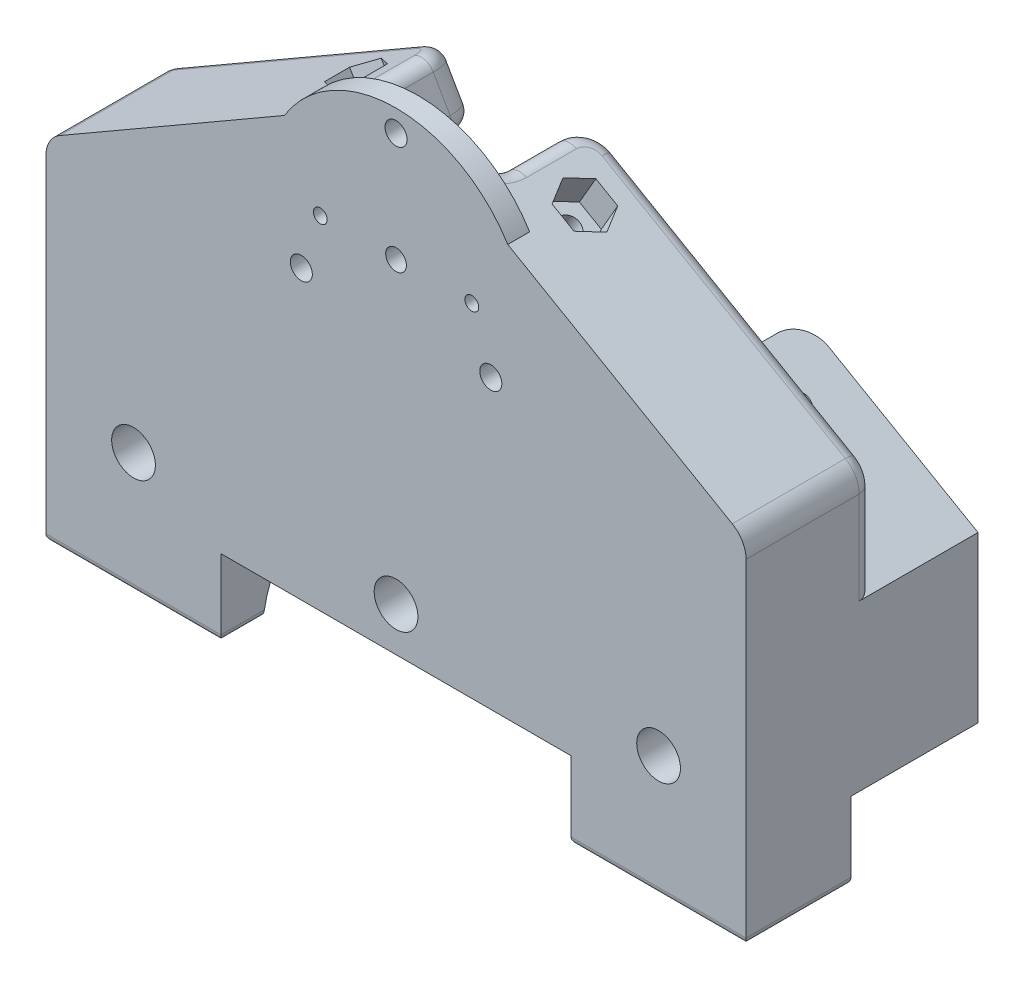
SolidWorks part; units mm, degrees
ref_plane "Front Plane" through (0, 0, 0) normal (0, 0, 1) x (1, 0, 0)
ref_plane "Top Plane" through (0, 0, 0) normal (0, 1, 0) x (1, 0, 0)
ref_plane "Right Plane" through (0, 0, 0) normal (1, 0, 0) x (0, 0, -1)
sketch "Sketch1" plane through (0, 0, 0) normal (0, 0, 1) x (1, 0, 0)
  line L0 (0, 0) -> (101.6, 0)
  line L2 (17.3289, 36.6882) -> (44.45, 52.3466) construction
  line L3 (0, 23.9337) -> (0, 0)
  line L5 (101.6, 23.9337) -> (101.6, 0)
  line L6 (25.1187, 38.436) -> (29.5637, 30.737)
  line L9 (0, 23.9337) -> (25.1187, 38.436)
  line L12 (44.45, 52.3466) -> (57.15, 52.3466) construction
  line L13 (50.8, -80.4066) -> (50.8, 0) construction
  line L14 (29.5637, 30.737) -> (9.3212, 19.05)
  line L16 (16.1383, 38.7504) -> (18.5196, 34.626) construction
  line L19 (17.3289, 36.6882) -> (12.7, 34.0157) construction
  line L20 (50.8, 39.3607) -> (50.8, 34.0157) construction
  line L23 (88.9, 34.0157) -> (12.7, 34.0157) construction
  line L25 (9.3212, 19.05) -> (92.2788, 19.05)
  line L27 (72.0363, 30.737) -> (92.2788, 19.05)
  line L30 (101.6, 23.9337) -> (76.4813, 38.436)
  line L33 (76.4813, 38.436) -> (72.0363, 30.737)
  line L36 (57.15, 52.3466) -> (148.0783, -0.1509) construction
  line L39 (50.8, 52.3466) -> (50.8, 37.7065) construction
  point P43 (50.8, -46.2816)
  dimension "D2" = 38.1
  dimension "D3" = 101.6
  dimension "D4" = 34.0157
  dimension "D5" = 19.05
  dimension "D6" = 5.3451
  dimension "D7" = 8.89
  dimension "D8" = 4.7625
  dimension "D9" = 4.7625
  dimension "D10" = 30
  dimension "D11" = 7.62
  dimension "D13" = 12.7
extrude "Boss-Extrude1" add sketch "Sketch1" along normal blind 15.24
sketch "Sketch5" plane through (35.7636, 61.9444, 0) normal (0.5, 0.866, 0) x (0, 0, -1)
  line L0 (-7.62, -47.0168) -> (-7.62, -54.6368) construction
  line L2 (-15.24, -47.0168) -> (0, -47.0168) construction
  circle A0 centre (-7.62, -54.6368) radius 1.5875
  dimension "D1" = 3.175
  dimension "D2" = 7.62
extrude "Cut-Extrude2" cut sketch "Sketch5" against normal up to surface (8.89 mm away) up to face at (82.1576, 24.8935, 7.62)
sketch "Sketch6" plane through (-10.3636, 17.9503, 0) normal (-0.5, 0.866, 0) x (0, 0, 1)
  line L0 (7.62, 40.9714) -> (7.62, 33.3514) construction
  line L2 (15.24, 40.9714) -> (0, 40.9714) construction
  circle A0 centre (7.62, 33.3514) radius 1.5875
  dimension "D2" = 3.175
  dimension "D1" = 7.62
extrude "Cut-Extrude3" cut sketch "Sketch6" against normal up to surface (8.89 mm away) up to face at (19.4424, 24.8935, 7.62)
sketch "Sketch7" plane through (0, 0, 15.24) normal (0, 0, 1) x (1, 0, 0)
  line L0 (101.6, 23.9337) -> (76.4813, 38.436) construction
  line L1 (0, 0) -> (101.6, 0)
  line L2 (0, 0) -> (0, 39.6983)
  line L3 (25.1187, 19.05) -> (76.4813, 19.05)
  line L4 (25.1187, 38.436) -> (0, 23.9337) construction
  line L5 (45.2295, 55.5462) -> (32.0313, 47.9262)
  line L6 (32.0313, 47.9262) -> (22.7374, 42.5604)
  line L7 (92.2788, 19.05) -> (9.3212, 19.05) construction
  line L8 (78.8626, 42.5604) -> (69.5687, 47.9262)
  line L9 (25.1187, 38.436) -> (0, 23.9337) construction
  line L10 (38.6304, 51.7362) -> (39.8211, 49.674) construction
  line L12 (44.45, 52.3466) -> (-1.9075, 25.582) construction
  line L14 (50.8, 11.2326) -> (50.8, 0) construction
  line L15 (44.45, 52.3466) -> (50.8, 52.3466) construction
  line L17 (50.8, 52.3466) -> (57.15, 52.3466) construction
  line L18 (57.15, 52.3466) -> (103.5075, 25.582) construction
  line L20 (25.1187, 38.436) -> (0, 23.9337) construction
  line L21 (45.2295, 55.5462) -> (40.7845, 63.2452)
  line L22 (40.7845, 63.2452) -> (0, 39.6983)
  line L26 (29.5637, 30.737) -> (25.1187, 38.436) construction
  line L32 (50.8, 52.3466) -> (50.8, 55.312) construction
  line L33 (22.7374, 42.5604) -> (25.1187, 38.436)
  line L36 (57.15, 52.3466) -> (103.5075, 25.582) construction
  line L39 (78.8626, 42.5604) -> (76.4813, 38.436)
  line L42 (60.8155, 63.2452) -> (101.6, 39.6983)
  line L43 (56.3705, 55.5462) -> (60.8155, 63.2452)
  line L46 (56.3705, 55.5462) -> (69.5687, 47.9262)
  line L47 (101.6, 0) -> (101.6, 39.6983)
  line L48 (25.1187, 38.436) -> (25.1187, 19.05)
  line L49 (76.4813, 38.436) -> (76.4813, 19.05)
  dimension "D1" = 6.35
  dimension "D3" = 15.24
  dimension "D7" = 2.3813
  dimension "D8" = 5.3451
  dimension "D9" = 2.3813
  dimension "D11" = 2.3813
extrude "Boss-Extrude4" add sketch "Sketch7" along normal blind 15.24
sketch "Sketch8" plane through (-12.7448, 22.0747, 0) normal (0.5, -0.866, 0) x (0, 0, -1)
  line L0 (-22.86, 66.9431) -> (-22.86, 59.3231) construction
  line L1 (-30.48, 66.9431) -> (-15.24, 66.9431) construction
  circle A0 centre (-22.86, 59.3231) radius 1.5875
  dimension "D2" = 3.175
  dimension "D1" = 7.62
extrude "Cut-Extrude4" cut sketch "Sketch8" against normal blind 12.7
sketch "Sketch9" plane through (38.1448, 66.0688, 0) normal (-0.5, -0.866, 0) x (0, 0, 1)
  line L0 (22.86, -21.0451) -> (22.86, -28.6651) construction
  line L1 (30.48, -21.0451) -> (15.24, -21.0451) construction
  circle A0 centre (22.86, -28.6651) radius 1.5875
  dimension "D1" = 3.175
  dimension "D2" = 7.62
extrude "Cut-Extrude5" cut sketch "Sketch9" against normal blind 12.7
sketch "Sketch13" plane through (0, 0, 30.48) normal (0, 0, 1) x (1, 0, 0)
  line L0 (33.9835, 49.0533) -> (35.1741, 46.9911) construction
  line L1 (22.7374, 42.5604) -> (45.2295, 55.5462) construction
  line L2 (50.8, 44.3186) -> (50.8, 0) construction
  line L3 (0, 0) -> (101.6, 0) construction
  line L6 (39.8031, 49.6636) -> (35.1741, 46.9911) construction
  line L7 (50.8, 44.3186) -> (50.8, 49.6636) construction
  line L8 (50.8, 49.6636) -> (39.8031, 49.6636) construction
  line L10 (61.7969, 49.6636) -> (50.8, 49.6636) construction
  dimension "D1" = 5.3451
  dimension "D2" = 2.3813
  dimension "D3" = 5.3451
sketch "Sketch14" plane through (0, 0, 0) normal (0, 0, -1) x (-1, 0, 0)
  line L0 (-83.0804, 34.626) -> (-85.4617, 38.7504) construction
  line L2 (-84.2711, 36.6882) -> (-88.9, 34.0157) construction
  line L3 (-88.9, 34.0157) -> (-50.8, 34.0157) construction
  line L4 (-50.8, 44.3186) -> (-50.8, 49.6636) construction
  line L5 (-50.8, 34.0157) -> (-12.7, 34.0157) construction
  line L6 (-76.4813, 38.436) -> (-72.0363, 30.737) construction
  line L7 (-101.6, 23.9337) -> (-76.4813, 38.436) construction
  dimension "D1" = 5.3451
  dimension "D2" = 4.7625
  dimension "D3" = 7.62
sketch "Sketch15" plane through (42.5898, 73.7678, 0) normal (0.5, 0.866, 0) x (0, 0, -1)
  line L0 (-22.86, -28.6651) -> (-19.685, -28.6651) construction
  line L1 (-19.685, -26.832) -> (-19.685, -30.4982)
  line L2 (-19.685, -26.832) -> (-22.86, -24.999)
  line L3 (-22.86, -24.999) -> (-26.035, -26.832)
  line L4 (-26.035, -26.832) -> (-26.035, -30.4982)
  line L5 (-26.035, -30.4982) -> (-22.86, -32.3313)
  line L6 (-22.86, -32.3313) -> (-19.685, -30.4982)
  line L7 (-21.2725, -25.9155) -> (-22.86, -28.6651) construction
  line L8 (-22.86, -28.6651) -> (-24.4475, -31.4148) construction
  dimension "D1" = 6.35
extrude "Cut-Extrude9" cut sketch "Sketch15" against normal blind 4.7625
sketch "Sketch16" plane through (31.3186, 54.2454, 0) normal (0.5, 0.866, 0) x (0, 0, -1)
  line L0 (-7.62, -54.6368) -> (-4.445, -54.6368) construction
  line L1 (-4.445, -52.8037) -> (-4.445, -56.4699)
  line L2 (-4.445, -52.8037) -> (-7.62, -50.9706)
  line L3 (-7.62, -50.9706) -> (-10.795, -52.8037)
  line L4 (-10.795, -52.8037) -> (-10.795, -56.4699)
  line L5 (-10.795, -56.4699) -> (-7.62, -58.3029)
  line L6 (-7.62, -58.3029) -> (-4.445, -56.4699)
  line L7 (-6.0325, -51.8871) -> (-7.62, -54.6368) construction
  line L8 (-7.62, -54.6368) -> (-9.2075, -57.3864) construction
  circle A0 centre (-7.62, -54.6368) radius 1.5875 construction
  dimension "D1" = 6.35
extrude "Cut-Extrude10" cut sketch "Sketch16" along normal blind 4.7625
sketch "Sketch17" plane through (-5.9186, 10.2513, 18.8617) normal (-0.5, 0.866, 0) x (-0.2962, -0.171, 0.9397)
  line L0 (-21.9706, 27.4952) -> (-18.7956, 27.4952) construction
  line L1 (-18.7956, 29.3283) -> (-18.7956, 25.6621)
  line L2 (-18.7956, 29.3283) -> (-21.9706, 31.1614)
  line L3 (-21.9706, 31.1614) -> (-25.1456, 29.3283)
  line L4 (-25.1456, 29.3283) -> (-25.1456, 25.6621)
  line L5 (-25.1456, 25.6621) -> (-21.9706, 23.829)
  line L6 (-21.9706, 23.829) -> (-18.7956, 25.6621)
  line L7 (-20.3831, 30.2448) -> (-21.9706, 27.4952) construction
  line L8 (-21.9706, 27.4952) -> (-23.5581, 24.7456) construction
  circle A2 centre (-21.9706, 27.4952) radius 1.5875 construction
  dimension "D1" = 6.35
extrude "Cut-Extrude11" cut sketch "Sketch17" along normal blind 4.7625
sketch "Sketch21" plane through (-66.0998, 1.5355, 0) normal (0.5, -0.866, 0) x (0.866, 0.5, 0)
  line L0 (115.7994, 22.86) -> (118.9744, 22.86) construction
  line L1 (118.9744, 24.6931) -> (118.9744, 21.0269)
  line L2 (118.9744, 24.6931) -> (115.7994, 26.5262)
  line L3 (115.7994, 26.5262) -> (112.6244, 24.6931)
  line L4 (112.6244, 24.6931) -> (112.6244, 21.0269)
  line L5 (112.6244, 21.0269) -> (115.7994, 19.1938)
  line L6 (115.7994, 19.1938) -> (118.9744, 21.0269)
  line L7 (117.3869, 25.6096) -> (115.7994, 22.86) construction
  line L8 (115.7994, 22.86) -> (114.2119, 20.1104) construction
  circle A0 centre (115.7994, 22.86) radius 1.5875 construction
  dimension "D1" = 6.35
extrude "Cut-Extrude16" cut sketch "Sketch21" along normal blind 4.7625
sketch "Sketch23" plane through (0, 0, 30.48) normal (0, 0, 1) x (1, 0, 0)
  line L0 (39.8031, 49.6636) -> (50.8, 49.6636) construction
  line L2 (50.8, 49.6636) -> (61.7969, 49.6636) construction
  line L3 (34.5883, 59.6678) -> (0, 39.6983)
  line L4 (67.0117, 59.6678) -> (101.6, 39.6983)
  line L5 (101.6, 39.6983) -> (101.6, 0)
  line L6 (101.6, 0) -> (0, 0)
  line L7 (0, 0) -> (0, 39.6983)
  line L8 (40.7845, 63.2452) -> (0, 39.6983) construction
  line L9 (101.6, 0) -> (101.6, 39.6983) construction
  line L10 (101.6, 39.6983) -> (60.8155, 63.2452) construction
  line L11 (50.8, 44.3186) -> (50.8, 49.6636) construction
  arc A0 (34.5883, 59.6678) -> (67.0117, 59.6678) centre (50.8, 49.6636) cw
  circle A1 centre (50.8, 49.6636) radius 1.5
  dimension "D1" = 3
  dimension "D2" = 19.05
extrude "Boss-Extrude5" add sketch "Sketch23" along normal blind 3.175
hole_wizard "M3 Clearance Hole1" positions "Sketch26" profile "Sketch25" hole size "M3" standard "Ansi Metric"
sketch "Sketch26" plane through (0, 0, 33.655) normal (0, 0, 1) x (1, 0, 0)
  line L0 (50.8, 65.5386) -> (37.0518, 41.7261) construction
  line L1 (37.0518, 41.7261) -> (64.5482, 41.7261) construction
  line L2 (64.5482, 41.7261) -> (50.8, 65.5386) construction
  line L4 (37.0518, 41.7261) -> (50.8, 49.6636) construction
  line L5 (50.8, 49.6636) -> (50.8, 0) construction
  line L8 (50.8, 49.6636) -> (64.5482, 41.7261) construction
  line L10 (50.8, 49.6636) -> (50.8, 65.5386) construction
  line L12 (0, 0) -> (101.6, 0) construction
  circle A1 centre (50.8, 49.6636) radius 1.5 construction
  point P0 (37.0518, 41.7261)
  point P1 (64.5482, 41.7261)
  point P3 (50.8, 65.5386)
  dimension "D1" = 15.875
sketch "Sketch25" plane through (37.0518, 41.7261, 33.655) normal (1, 0, 0) x (0, -1, 0)
  line L0 (0, 0) -> (0, 10.8674)
  line L1 (0, 10.8674) -> (1.6, 9.906)
  line L2 (1.6, 9.906) -> (1.6, 0)
  line L5 (1.6, 0) -> (0, 0)
  line L10 (0, 10.8674) -> (-1.6, 9.906) construction
  line L11 (0, -6.35) -> (0, 107.95) construction
  dimension "Hole Dia." = 3.2
  dimension "Hole Depth" = 9.906
  dimension "Drill Angle" = 118
sketch "Sketch27" plane through (0, 0, 33.655) normal (0, 0, 1) x (1, 0, 0)
  circle A0 centre (39.8031, 49.6636) radius 1
  circle A1 centre (61.7969, 49.6636) radius 1
  circle A2 centre (50.8, 49.6636) radius 1
  dimension "D1" = 2
extrude "Cut-Extrude18" cut sketch "Sketch27" along direction (0, 0, -1) on the side against the normal through all
sketch "Sketch22" plane through (0, 0, 0) normal (0, 0, -1) x (-1, 0, 0)
  line L0 (-50.8, 0) -> (-50.8, 6.35) construction
  line L1 (0, 0) -> (-101.6, 0) construction
  line L2 (-50.8, 6.35) -> (-88.9, 6.35) construction
  line L3 (-50.8, 6.35) -> (-12.7, 6.35) construction
  line L4 (-92.2788, 19.05) -> (-9.3212, 19.05) construction
  circle A0 centre (-88.9, 6.35) radius 3.175
  circle A1 centre (-50.8, 6.35) radius 3.175
  circle A2 centre (-12.7, 6.35) radius 3.175
  dimension "D1" = 6.35
  dimension "D2" = 38.1
  dimension "D3" = 12.7
extrude "Cut-Extrude17" cut sketch "Sketch22" against normal through all
hole_wizard "CBORE for M3 SHCS1" positions "Sketch29" profile "Sketch28" counterbore size "M3" standard "Ansi Metric" end condition through all
sketch "Sketch29" plane through (2.2303, 19.05, 8.3927) normal (0, -1, 0) x (1, 0, 0)
  line L0 (32.6947, -2.0427) -> (64.4447, -2.0427) construction
  line L2 (48.5697, -2.0427) -> (48.5697, -8.3927) construction
  line L4 (-2.2303, -8.3927) -> (99.3697, -8.3927) construction
  point P0 (64.4447, -2.0427)
  point P1 (32.6947, -2.0427)
  dimension "D1" = 6.35
  dimension "D2" = 31.75
sketch "Sketch28" plane through (66.675, 19.05, 6.35) normal (1, 0, 0) x (0, 0, 1)
  line L0 (0, 0) -> (0, 19.05)
  line L1 (0, 19.05) -> (1.6, 19.05)
  line L3 (1.6, 19.05) -> (1.6, 3)
  line L4 (1.6, 3) -> (3.25, 3)
  line L5 (3.25, 3) -> (3.25, 0)
  line L7 (3.25, 0) -> (0, 0)
  line L11 (0, -6.35) -> (0, 107.95) construction
  dimension "Thru Hole Dia." = 3.2
  dimension "Thru Hole Depth" = 19.05
  dimension "C'Bore Dia." = 6.5
  dimension "C'Bore Depth" = 3
sketch "Sketch31" plane through (0, 0, 0) normal (0, -1, 0) x (1, 0, 0)
  line L0 (25.4, 18.415) -> (76.2, 18.415) construction
  line L1 (0, 33.655) -> (25.4, 33.655)
  line L2 (0, 33.655) -> (0, 18.415)
  line L3 (0, 18.415) -> (25.4, 18.415)
  line L4 (25.4, 33.655) -> (25.4, 18.415)
  line L5 (101.6, 33.655) -> (76.2, 33.655)
  line L6 (101.6, 33.655) -> (101.6, 18.415)
  line L7 (101.6, 18.415) -> (76.2, 18.415)
  line L8 (76.2, 33.655) -> (76.2, 18.415)
  line L9 (50.8, 18.415) -> (50.8, 33.655) construction
  line L10 (0, 33.655) -> (101.6, 33.655) construction
  dimension "D1" = 50.8
  dimension "D2" = 15.24
extrude "Boss-Extrude7" add sketch "Sketch31" along normal blind 11.2
fillet "Fillet5" radius 4 14 edges at (72.0363, 30.737, 7.62) (74.2588, 34.5865, 0) (50.8, 19.05, 30.48) (25.1187, 28.743, 30.48) (76.4813, 28.743, 30.48) (0, 39.6983, 24.4475) (29.5637, 30.737, 7.62) (27.3412, 34.5865, 0) (58.593, 59.3957, 30.48) (43.007, 59.3957, 30.48) (43.007, 59.3957, 15.24) (58.593, 59.3957, 15.24) (101.6, 39.6983, 24.4475)
fillet "Fillet3" radius 3 3 edges at (26.2903, 20.2216, 15.24)
fillet "Fillet6" radius 1 8 edges at (88.9, -11.2, 18.415) (76.2, -11.2, 26.035) (88.9, -11.2, 33.655) (101.6, -11.2, 26.035) (12.7, -11.2, 33.655) (25.4, -11.2, 26.035) (12.7, -11.2, 18.415) (0, -11.2, 26.035)
fillet "Fillet7" radius 2 20 edges at (56.3705, 55.5462, 22.86) (60.8155, 63.2452, 22.86) (40.7845, 63.2452, 22.86) (45.2295, 55.5462, 22.86) (55.3558, 56.132, 29.3084) (69.3486, 48.0533, 15.24) (57.3851, 54.9605, 16.4116) (101.0641, 39.3888, 15.24) (81.9398, 51.0491, 15.24) (61.8301, 62.6594, 16.4116) (59.8008, 63.831, 29.3084) (41.7992, 63.831, 29.3084) (0.5359, 39.3888, 15.24) (19.6602, 51.0491, 15.24) (39.7699, 62.6594, 16.4116) (46.2442, 56.132, 29.3084) (32.2514, 48.0533, 15.24) (44.2149, 54.9605, 16.4116)
sketch "Sketch32" plane through (-12.7448, 22.0747, 0) normal (0.5, -0.866, 0) x (0.866, 0.5, 0)
  circle A0 centre (59.3231, 22.86) radius 4.7625
  dimension "D1" = 9.525
extrude "Cut-Extrude19" cut sketch "Sketch32" along normal blind 90.424
sketch "Sketch33" plane through (38.1448, 66.0688, 0) normal (-0.5, -0.866, 0) x (0.866, -0.5, 0)
  circle A0 centre (28.6651, 22.86) radius 4.7625
  dimension "D1" = 9.525
extrude "Cut-Extrude20" cut sketch "Sketch33" along normal blind 90.424
